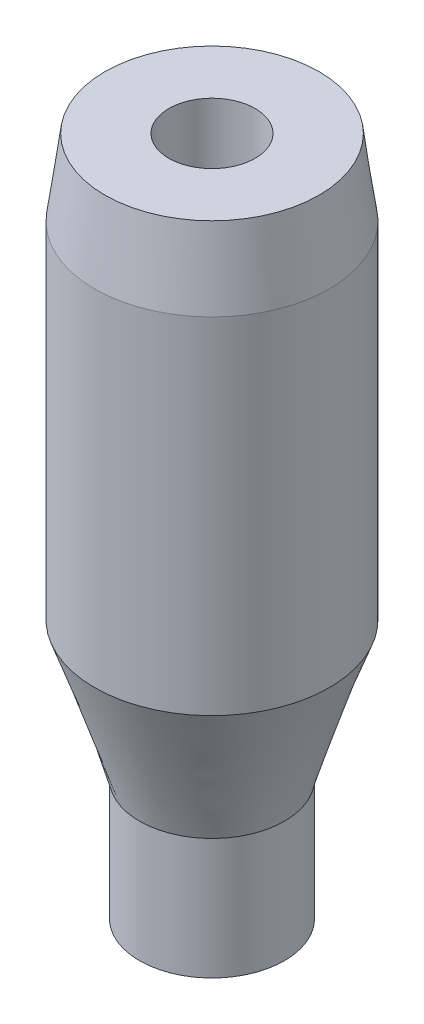
SolidWorks part; units mm, degrees
ref_plane "前视基准面" through (0, 0, 0) normal (0, 0, 1) x (1, 0, 0)
ref_plane "上视基准面" through (0, 0, 0) normal (0, 1, 0) x (1, 0, 0)
ref_plane "右视基准面" through (0, 0, 0) normal (1, 0, 0) x (0, 0, -1)
sketch "草图1" plane through (0, 0, 0) normal (0, 1, 0) x (1, 0, 0)
  circle A0 centre (0, 0) radius 2.1
extrude "凸台-拉伸1" add sketch "草图1" along normal blind 7.5
ref_plane "基准面1" through (0, 3.5, 0) normal (0, 1, 0) x (1, 0, 0)
sketch "草图3" plane through (0, 7.5, 0) normal (0, 1, 0) x (1, 0, 0)
  circle A0 centre (0, 0) radius 3.4
sketch "草图4" plane through (0, 3.5, 0) normal (0, 1, 0) x (1, 0, 0)
  circle A0 centre (0, 0) radius 2.1
loft "放样1" add profiles "草图3", "草图4" connector at (-3.3881, 7.5, 0.2838) connector at (-1.8945, 3.5, 0.9061)
sketch "草图5" plane through (0, 7.5, 0) normal (0, 1, 0) x (1, 0, 0)
  circle A0 centre (0, 0) radius 3.4
extrude "凸台-拉伸2" add sketch "草图5" along normal blind 10
sketch "草图6" plane through (0, 17.5, 0) normal (0, 1, 0) x (1, 0, 0)
  circle A0 centre (0, 0) radius 3.4
ref_plane "基准面2" through (0, 19.7, 0) normal (0, 1, 0) x (1, 0, 0)
sketch "草图7" plane through (0, 19.7, 0) normal (0, 1, 0) x (1, 0, 0)
  circle A0 centre (0, 0) radius 3.1
loft "放样2" add profiles "草图7", "草图6" connector at (-2.9972, 19.7, -0.7917) connector at (-3.2772, 17.5, -0.9054)
sketch "草图8" plane through (0, 19.7, 0) normal (0, 1, 0) x (1, 0, 0)
  circle A0 centre (0, 0) radius 1.25
extrude "切除-拉伸1" cut sketch "草图8" against normal through all
